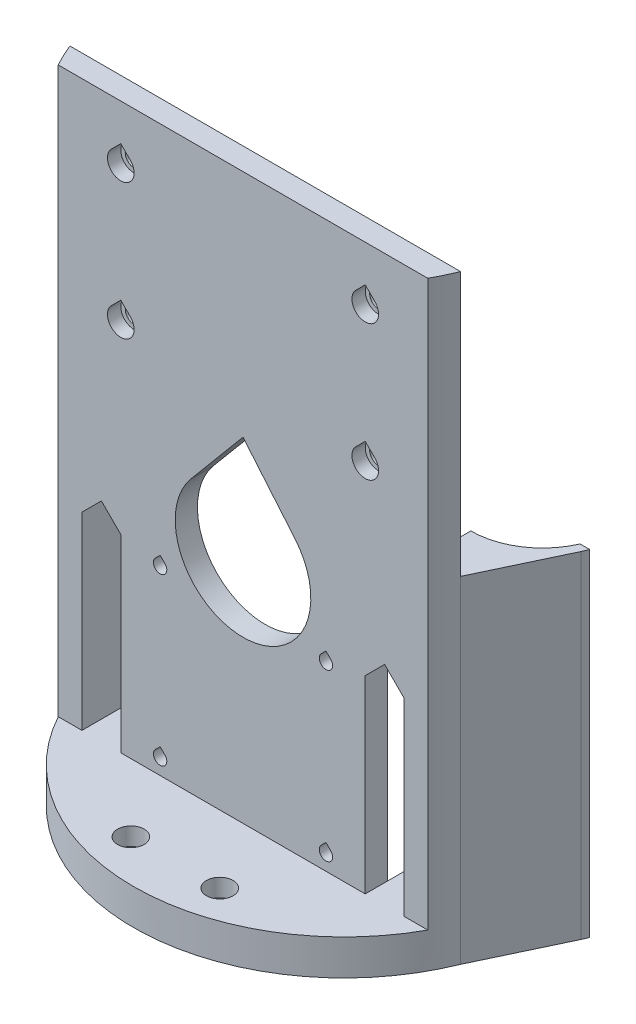
SolidWorks part; units mm, degrees
ref_plane "Front Plane" through (0, 0, 0) normal (0, 0, 1) x (1, 0, 0)
ref_plane "Top Plane" through (0, 0, 0) normal (0, 1, 0) x (1, 0, 0)
ref_plane "Right Plane" through (0, 0, 0) normal (1, 0, 0) x (0, 0, -1)
sketch "Sketch3" plane through (0, 0, 0) normal (0, 1, 0) x (1, 0, 0)
  line L0 (-43.9425, -17.7712) -> (43.9425, -17.7712)
  line L1 (-41.572, -22.7712) -> (41.572, -22.7712)
  arc A0 (-43.9425, -17.7712) -> (-41.572, -22.7712) centre (0, 0) ccw
  arc A1 (41.572, -22.7712) -> (43.9425, -17.7712) centre (0, 0) ccw
  dimension "D1" = 47.4
  dimension "D2" = 17.7712
  dimension "D3" = 5
extrude "Boss-Extrude2" add sketch "Sketch3" along normal blind 135
sketch "Sketch4" plane through (0, 0, 0) normal (0, 1, 0) x (1, 0, 0)
  line L0 (43.9425, -17.7712) -> (-43.9425, -17.7712) construction
  line L1 (0, -17.7712) -> (0, 19.754) construction
  line L2 (-36.2, 8.4288) -> (36.2, 8.4288) construction
  line L3 (-43.9425, -17.7712) -> (-52.653, 0.6482)
  line L7 (-43.9425, -17.7712) -> (-36.238, -17.7712)
  line L9 (-51.0678, 1.9955) -> (-53.2251, 1.9955)
  line L16 (30.2222, -17.7712) -> (-43.9425, -17.7712)
  line L21 (43.9425, -17.7712) -> (-43.9425, -17.7712) construction
  line L22 (-36.238, -17.7712) -> (-36.238, -10.4482)
  line L23 (-36.238, -10.4482) -> (-36.238, -7.7711)
  line L24 (36.238, -10.4482) -> (36.238, -7.7711)
  line L25 (36.238, -17.7712) -> (36.238, -10.4482)
  line L26 (51.0678, 1.9955) -> (53.2251, 1.9955)
  line L27 (43.9425, -17.7712) -> (36.238, -17.7712)
  line L28 (43.9425, -17.7712) -> (52.653, 0.6482)
  arc A1 (-53.2251, 1.9955) -> (-52.653, 0.6482) centre (-36.2, 8.4288) ccw
  arc A2 (-51.0678, 1.9955) -> (-36.238, -7.7711) centre (-36.2, 8.4288) ccw
  arc A4 (51.0678, 1.9955) -> (36.238, -7.7711) centre (36.2, 8.4288) cw
  circle A5 centre (-36.2, 8.4288) radius 18.2 construction
  arc A6 (53.2251, 1.9955) -> (52.653, 0.6482) centre (36.2, 8.4288) cw
  circle A7 centre (-36.2, 8.4288) radius 16.2 construction
  point P8 (0, 8.4288)
  dimension "D3" = 2
  dimension "D4" = 32.4
extrude "Boss-Extrude4" add sketch "Sketch4" along normal blind 75.6 contours L3 A1 L9 A2 L23 L22 L7 | A4 L24 L25 L27 L28 A6 L26
sketch "Sketch5" plane through (0, 0, 22.7712) normal (0, 0, 1) x (1, 0, 0)
  line L0 (0, 135) -> (0, 0) construction
  line L1 (-41.572, 135) -> (41.572, 135) construction
  line L2 (-41.572, 0) -> (41.572, 0) construction
  line L3 (-28.9142, 123.8642) -> (-27.5, 125.2784)
  line L4 (-27.5, 125.2784) -> (-26.0858, 123.8642)
  line L5 (-28.9142, 123.8642) -> (-23.9559, 123.8642) construction
  line L6 (26.0858, 123.8642) -> (27.5, 125.2784)
  line L7 (27.5, 125.2784) -> (28.9142, 123.8642)
  line L8 (26.0858, 123.8642) -> (30.7355, 123.8642) construction
  line L9 (-28.9142, 93.3642) -> (-27.5, 94.7784)
  line L10 (-27.5, 94.7784) -> (-26.0858, 93.3642)
  line L11 (-28.9142, 93.3642) -> (-24.01, 93.3642) construction
  line L12 (26.0858, 93.3642) -> (27.5, 94.7784)
  line L13 (27.5, 94.7784) -> (28.9142, 93.3642)
  line L14 (26.0858, 93.3642) -> (30.8575, 93.3642) construction
  line L16 (43.9425, 75.6) -> (52.653, 75.6) construction
  line L17 (-27.5, 122.45) -> (27.5, 122.45) construction
  line L18 (-27.5, 122.45) -> (-27.5, 91.95) construction
  line L19 (-27.5, 91.95) -> (27.5, 91.95) construction
  line L20 (27.5, 122.45) -> (27.5, 91.95) construction
  arc A0 (-28.9142, 123.8642) -> (-26.0858, 123.8642) centre (-27.5, 122.45) ccw
  arc A1 (26.0858, 123.8642) -> (28.9142, 123.8642) centre (27.5, 122.45) ccw
  arc A2 (-28.9142, 93.3642) -> (-26.0858, 93.3642) centre (-27.5, 91.95) ccw
  arc A3 (26.0858, 93.3642) -> (28.9142, 93.3642) centre (27.5, 91.95) ccw
  point P29 (0, 122.45)
  dimension "D1" = 4
  dimension "D4" = 30.5
  dimension "D2" = 55
  dimension "D3" = 16.35
  dimension "D6" = 45
  dimension "D7" = 45
  dimension "D8" = 45
  dimension "D9" = 45
extrude "Cut-Extrude2" cut sketch "Sketch5" against normal up to next
sketch "Sketch6" plane through (0, 0, 0) normal (0, -1, 0) x (1, 0, 0)
  line L0 (-41.572, 22.7712) -> (41.572, 22.7712)
  line L15 (-36.238, 17.7712) -> (36.238, 17.7712)
  line L16 (-36.238, 17.7712) -> (-36.238, 7.7711)
  line L17 (-36.238, 7.7711) -> (36.238, 7.7711)
  line L18 (36.238, 17.7712) -> (36.238, 7.7711)
  arc A0 (41.572, 22.7712) -> (-41.572, 22.7712) centre (0, 0) ccw
  arc A1 (43.9425, 17.7712) -> (41.572, 22.7712) centre (0, 0) ccw construction
extrude "Boss-Extrude5" add sketch "Sketch6" against normal blind 8
sketch "Sketch7" plane through (0, 8, 0) normal (0, 1, 0) x (1, 0, 0)
  line L0 (-36.238, -7.7711) -> (36.238, -7.7711) construction
  line L1 (-36.238, -17.7712) -> (-36.238, -7.7711) construction
  line L2 (36.238, -17.7712) -> (36.238, -7.7711) construction
  circle A0 centre (-10, -38) radius 2
  circle A1 centre (10, -38) radius 2
  circle A2 centre (-31.0922, -12.7711) radius 2
  circle A3 centre (31.088, -12.7711) radius 2
  circle A4 centre (-31.0922, -12.7711) radius 3.25 construction
  dimension "D1" = 4
  dimension "D2" = 6.5
  dimension "D3" = 5.1458
  dimension "D4" = 5
  dimension "D5" = 38
  dimension "D6" = 5.15
  dimension "D7" = 10
  dimension "D8" = 10
extrude "Cut-Extrude3" cut sketch "Sketch7" against normal blind 15
sketch "Sketch9" plane through (0, 0, 17.7712) normal (0, 0, -1) x (-1, 0, 0)
  line L0 (-11.6869, 69.3157) -> (0, 83.2436)
  line L5 (0, 83.2436) -> (11.6869, 69.3157)
  line L6 (-14.7324, 55.5461) -> (-3.8891, 55.5461) construction
  arc A0 (-11.6869, 69.3157) -> (11.6869, 69.3157) centre (0, 59.5093) ccw
  dimension "D1" = 50
extrude "Cut-Extrude5" cut sketch "Sketch9" against normal up to next
sketch "Sketch10" plane through (0, 8, 0) normal (0, 1, 0) x (1, 0, 0)
  circle A0 centre (-10, -38) radius 3
  circle A1 centre (10, -38) radius 3
  circle A2 centre (31.088, -12.7711) radius 3
  circle A3 centre (-31.0922, -12.7711) radius 3
  dimension "D1" = 6
extrude "Cut-Extrude6" cut sketch "Sketch10" against normal blind 4
sketch "Sketch11" plane through (0, 0, 22.7712) normal (0, 0, 1) x (1, 0, 0)
  line L1 (-27.5, 125.2784) -> (-28.9142, 123.8642) construction
  line L2 (-26.0858, 123.8642) -> (-27.5, 125.2784) construction
  line L3 (-27.5, 125.2784) -> (-28.9142, 123.8642)
  line L4 (-26.0858, 123.8642) -> (-27.5, 125.2784)
  line L5 (27.5, 125.2784) -> (26.0858, 123.8642) construction
  line L6 (27.5, 125.2784) -> (26.0858, 123.8642)
  line L7 (28.9142, 93.3642) -> (27.5, 94.7784) construction
  line L8 (27.5, 94.7784) -> (26.0858, 93.3642) construction
  line L9 (28.9142, 123.8642) -> (27.5, 125.2784) construction
  line L10 (28.9142, 93.3642) -> (27.5, 94.7784)
  line L11 (27.5, 94.7784) -> (26.0858, 93.3642)
  line L12 (28.9142, 123.8642) -> (27.5, 125.2784)
  line L13 (-26.0858, 93.3642) -> (-27.5, 94.7784) construction
  line L14 (-27.5, 94.7784) -> (-28.9142, 93.3642) construction
  line L15 (-26.0858, 93.3642) -> (-27.5, 94.7784)
  line L16 (-27.5, 94.7784) -> (-28.9142, 93.3642)
  line L17 (-27.5, 126.6926) -> (-29.6213, 124.5713)
  line L18 (-25.3787, 124.5713) -> (-27.5, 126.6926)
  line L19 (27.5, 126.6926) -> (25.3787, 124.5713)
  line L20 (29.6213, 124.5713) -> (27.5, 126.6926)
  line L21 (29.6213, 94.0713) -> (27.5, 96.1926)
  line L22 (27.5, 96.1926) -> (25.3787, 94.0713)
  line L23 (-25.3787, 94.0713) -> (-27.5, 96.1926)
  line L24 (-27.5, 96.1926) -> (-29.6213, 94.0713)
  arc A0 (-28.9142, 123.8642) -> (-26.0858, 123.8642) centre (-27.5, 122.45) ccw construction
  arc A1 (-28.9142, 123.8642) -> (-26.0858, 123.8642) centre (-27.5, 122.45) ccw
  arc A2 (26.0858, 93.3642) -> (28.9142, 93.3642) centre (27.5, 91.95) ccw construction
  arc A3 (26.0858, 123.8642) -> (28.9142, 123.8642) centre (27.5, 122.45) ccw construction
  arc A4 (26.0858, 93.3642) -> (28.9142, 93.3642) centre (27.5, 91.95) ccw
  arc A5 (26.0858, 123.8642) -> (28.9142, 123.8642) centre (27.5, 122.45) ccw
  arc A6 (-28.9142, 93.3642) -> (-26.0858, 93.3642) centre (-27.5, 91.95) ccw construction
  arc A7 (-28.9142, 93.3642) -> (-26.0858, 93.3642) centre (-27.5, 91.95) ccw
  arc A8 (-29.6213, 124.5713) -> (-25.3787, 124.5713) centre (-27.5, 122.45) ccw
  arc A9 (25.3787, 124.5713) -> (29.6213, 124.5713) centre (27.5, 122.45) ccw
  arc A10 (25.3787, 94.0713) -> (29.6213, 94.0713) centre (27.5, 91.95) ccw
  arc A11 (-29.6213, 94.0713) -> (-25.3787, 94.0713) centre (-27.5, 91.95) ccw
  dimension "D1" = 3
extrude "Cut-Extrude7" cut sketch "Sketch11" against normal blind 3
sketch "Sketch12" plane through (0, 0, 17.7712) normal (0, 0, -1) x (-1, 0, 0)
  line L0 (-36.238, 8) -> (36.238, 8) construction
  line L2 (-19.7107, 49.8607) -> (-18.65, 50.9213)
  line L3 (-18.65, 50.9213) -> (-17.5893, 49.8607)
  line L4 (17.5893, 49.8607) -> (18.65, 50.9213)
  line L5 (18.65, 50.9213) -> (19.7107, 49.8607)
  line L6 (-19.7107, 12.5607) -> (-18.65, 13.6213)
  line L7 (-18.65, 13.6213) -> (-17.5893, 12.5607)
  line L8 (17.5893, 12.5607) -> (18.2123, 12.5607) construction
  line L9 (17.5893, 12.5607) -> (18.65, 13.6213)
  line L10 (18.65, 13.6213) -> (19.7107, 12.5607)
  line L12 (-18.65, 48.8) -> (18.65, 48.8) construction
  line L13 (-18.65, 48.8) -> (-18.65, 11.5) construction
  line L14 (-18.65, 11.5) -> (18.65, 11.5) construction
  line L15 (18.65, 48.8) -> (18.65, 11.5) construction
  arc A0 (17.5893, 12.5607) -> (19.7107, 12.5607) centre (18.65, 11.5) ccw
  arc A1 (-19.7107, 12.5607) -> (-17.5893, 12.5607) centre (-18.65, 11.5) ccw
  arc A2 (-19.7107, 49.8607) -> (-17.5893, 49.8607) centre (-18.65, 48.8) ccw
  arc A3 (17.5893, 49.8607) -> (19.7107, 49.8607) centre (18.65, 48.8) ccw
  point P4 (0, 11.5)
  dimension "D1" = 3.5
  dimension "D5" = 37.3
  dimension "D6" = 45
extrude "Cut-Extrude8" cut sketch "Sketch12" against normal up to next
sketch "Sketch13" plane through (0, 0, 17.7712) normal (0, 0, -1) x (-1, 0, 0)
  line L9 (-36.238, 75.6) -> (-36.238, 8) construction
  line L10 (36.238, 8) -> (-36.238, 8) construction
  line L14 (-36.238, 50.5268) -> (-36.238, 8)
  line L15 (-36.238, 8) -> (-27.4841, 8)
  line L16 (-27.4841, 50.5268) -> (-27.4841, 8)
  line L17 (-27.4841, 50.5268) -> (-31.861, 54.9037)
  line L18 (-31.861, 54.9037) -> (-36.238, 50.5268)
  line L19 (-36.238, 50.5268) -> (-33.03, 50.5268) construction
  line L20 (0, 8) -> (0, 50.5268) construction
  line L21 (36.238, 50.5268) -> (33.03, 50.5268) construction
  line L22 (31.861, 54.9037) -> (36.238, 50.5268)
  line L23 (27.4841, 50.5268) -> (31.861, 54.9037)
  line L24 (27.4841, 50.5268) -> (27.4841, 8)
  line L25 (36.238, 8) -> (27.4841, 8)
  line L26 (36.238, 50.5268) -> (36.238, 8)
  point P12 (-31.861, 8)
  dimension "D1" = 45
extrude "Cut-Extrude9" cut sketch "Sketch13" against normal up to next
sketch "Sketch14" plane through (0, 8, 0) normal (0, 1, 0) x (1, 0, 0)
  line L0 (-36.238, -7.7711) -> (36.238, -7.7711) construction
  line L1 (-27.4841, -7.7711) -> (27.4841, -7.7711)
  line L2 (-27.4841, -7.7711) -> (-27.4841, -17.7712)
  line L3 (-27.4841, -17.7712) -> (27.4841, -17.7712)
  line L4 (27.4841, -7.7711) -> (27.4841, -17.7712)
  line L5 (43.9425, -17.7712) -> (-43.9425, -17.7712) construction
extrude "Cut-Extrude10" cut sketch "Sketch14" against normal up to next
